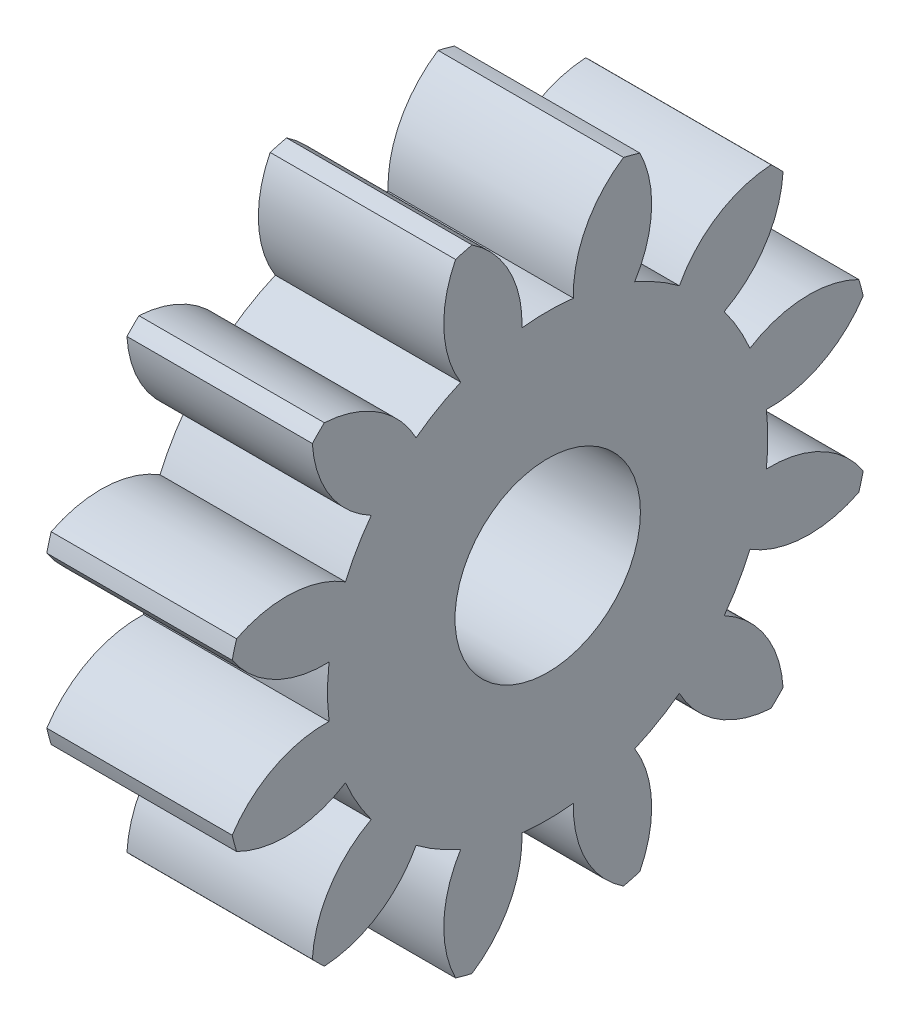
SolidWorks part; units mm, degrees
ref_plane "Plane1" through (0, 0, 0) normal (0, 0, 1) x (1, 0, 0)
ref_plane "Plane2" through (0, 0, 0) normal (0, 1, 0) x (1, 0, 0)
ref_plane "Plane3" through (0, 0, 0) normal (1, 0, 0) x (0, 0, -1)
sketch "HoldingSke" plane through (0, 0, 0) normal (0, 1, 0) x (1, 0, 0)
  line L0 (0, 0) -> (0.4891, -0.104)
  line L1 (-15, 0) -> (100, 0) construction
  line L2 (0, 0) -> (-2.1039, 2.3779)
  line L3 (0, 0) -> (-11.863, 4.5341)
  line L4 (0, 0) -> (8.4473, 1.7955)
  line L5 (0, 0) -> (-46.8476, -17.4728)
  line L6 (0, 0) -> (-6.6317, -4.4744)
  line L7 (-2.1039, 2.3779) -> (8.6586, 51.2059)
  line L8 (-76.2, 54.61) -> (-74.4, 54.61)
  line L9 (-71.009, 38.7566) -> (-53.1078, 45.2721)
  line L10 (-76.2, 71.12) -> (104.1128, 71.12)
  line L11 (0, 0) -> (-8, 0)
  line L12 (-76.2, 101.6) -> (-76.133, 101.6)
  line L13 (24.9733, 27.94) -> (52.9518, 28.4284)
  line L14 (24.9733, 27.94) -> (24.9743, 27.94)
  line L15 (24.9733, 27.94) -> (100.4006, 29.5858)
  line L16 (-63.627, -2) -> (-12.827, -2)
  circle A0 centre (0, 0) radius 5
  circle A1 centre (0, 0) radius 9.499
  circle A2 centre (0, 0) radius 37.5
  circle A3 centre (0, 0) radius 5
  dimension "Num_teeth" = 12
  dimension "Pitch_radius" = 180.3128
  dimension "Width" = 8
  dimension "Thickness" = 8
sketch "BasProSke" plane through (0, 0, 0) normal (0, 1, 0) x (1, 0, 0)
  line L0 (-10, 0) -> (60, 0) construction
  line L1 (0, 0) -> (0, 14)
  line L2 (0, 0) -> (8, 0)
  line L3 (8, 0) -> (8, 14)
  line L4 (8, 14) -> (0, 14)
  dimension "Thickness" = 8
  dimension "Diameter" = 28
revolve "Base-Revolve" add sketch "BasProSke" angle 360 about L0
sketch "TooCutSke" plane through (0, 0, 0) normal (1, 0, 0) x (0, 0, -1)
  line L1 (0, 0) -> (0, 107) construction
  line L2 (0, 0) -> (-1.6834, 11.8813) construction
  line L3 (0, 0) -> (-6.1662, 23.0126) construction
  line L4 (-1.6834, 11.8813) -> (-3.0831, 11.5063) construction
  arc A0 (1.1119, 9.4337) -> (-1.1119, 9.4337) centre (0, 0) ccw
  arc A1 (3.2981, 13.6321) -> (-3.2981, 13.6321) centre (0, 0) ccw
  circle A2 centre (0, 0) radius 12 construction
  circle A3 centre (0, 0) radius 11.2763 construction
  arc A4 (-1.1119, 9.4337) -> (-3.2981, 13.6321) centre (-5.9089, 9.6042) ccw
  arc A5 (3.2981, 13.6321) -> (1.1119, 9.4337) centre (5.9089, 9.6042) ccw
extrude "ToothCut" cut sketch "TooCutSke" along normal through all
fillet "Breaks" [suppressed] radius 0.04 tangent propagation no
fillet "RootFillets" [suppressed] radius 0.501
pattern_circular "TeethCuts" count 12 every 30 about axis through (-10, 0, 0) along (1, 0, 0) of "ToothCut", "RootFillets", "Breaks"
sketch "HubNeaOneSke" plane through (0, 0, 0) normal (-1, 0, 0) x (0, 0, 1)
  circle A0 centre (0, 0) radius 9.499
  dimension "Diameter" = 18.998
extrude "HubNearOne" [suppressed] add sketch "HubNeaOneSke" along normal blind 42.0001
sketch "HubNeaBotSke" plane through (0, 0, 0) normal (-1, 0, 0) x (0, 0, 1)
  circle A0 centre (0, 0) radius 9.499
  dimension "Diameter" = 18.998
extrude "HubNearBoth" [suppressed] add sketch "HubNeaBotSke" along normal blind 21
ref_plane "FarPln" through (8, 0, 0) normal (1, 0, 0) x (0, 0, -1)
sketch "HubFarSke" plane through (8, 0, 0) normal (1, 0, 0) x (0, 0, -1)
  circle A0 centre (0, 0) radius 9.499
  dimension "Diameter" = 18.998
extrude "HubFar" [suppressed] add sketch "HubFarSke" along normal blind 21
sketch "BorSke" plane through (0, 0, 0) normal (1, 0, 0) x (0, 0, -1)
  circle A0 centre (0, 0) radius 5
  dimension "Diameter" = 10
extrude "Bore" cut sketch "BorSke" along normal mid plane 100.0001
sketch "KeySke" plane through (0, 0, 0) normal (1, 0, 0) x (0, 0, -1)
  line L0 (-2, 0) -> (-2, 6.8)
  line L1 (-2, 6.8) -> (2, 6.8)
  line L2 (2, 6.8) -> (2, 0)
  line L3 (0, 0) -> (0, 34) construction
  line L4 (-2, 0) -> (2, 0)
  dimension "Width" = 4
extrude "Keyway" [suppressed] cut sketch "KeySke" along normal mid plane 100.0001
pattern_circular "Keyway2" [suppressed] count 2 every 90 about axis through (-10, 0, 0) along (1, 0, 0) reverse direction yes
sketch "Sketch1" plane through (8, 0, 0) normal (1, 0, 0) x (0, 0, -1)
  circle A0 centre (0, 0) radius 4
  circle A1 centre (0, 0) radius 5 construction
  circle A2 centre (0, 0) radius 5
  dimension "D1" = 8
extrude "Boss-Extrude1" add sketch "Sketch1" against normal through all
equation "' \"Module@HoldingSke\" = 6.35"
equation "' \"Num_teeth@HoldingSke\" = 12"
equation "' \"Ap@HoldingSke\" =  20"
equation "' \"Ap@HoldingSke\" = 20"
equation "' \"Width@HoldingSke\" = 0.5 * 25.4"
equation "' \"Hub_dia@HoldingSke\"= 1 * 25.4"
equation "' \"Hub_dia@HoldingSke\" = 1 * 25.4"
equation "' \"Overall_len@HoldingSke\" = 1.0 * 25.4"
equation "' \"Bore@HoldingSke\" = 0.75 * 25.4"
equation "' \"T_dim@HoldingSke\" = 0.1 * 25.4"
equation "' \"Width@KeySke\" = 0.25 * 25.4"
equation "' \"Show_teeth@HoldingSke\" = 13"
equation "' \"Backlash@HoldingSke\" = 0.009 * 25.4"
equation "' \"Addendum_fac@HoldingSke\" = 1.0"
equation "' \"Dedendum_fac@HoldingSke\" = 1.25"
equation "' \"Dedendum_add@HoldingSke\" = 0.00005 * 25.4"
equation "' \"Clearance_fac@HoldingSke\" = 0.25"
equation "\"Pitch@HoldingSke\" = 1 / \"Module@HoldingSke\""
equation "\"Overcut_dia@TooCutSke\" = (\"Num_teeth@HoldingSke\" + 2 * \"Addendum_fac@HoldingSke\") / \"Pitch@HoldingSke\" + 0.002 * 25.4"
equation "\"Pitch_dia@TooCutSke\" = \"Num_teeth@HoldingSke\" / \"Pitch@HoldingSke\""
equation "\"Base_dia@TooCutSke\" = \"Num_teeth@HoldingSke\" / \"Pitch@HoldingSke\" * cos((\"Ap@HoldingSke\"  * 3.14159265 / 180))"
equation "\"Root_dia@TooCutSke\" = (\"Num_teeth@HoldingSke\" + 2) / \"Pitch@HoldingSke\" - 2 * (\"Addendum_fac@HoldingSke\" + \"Dedendum_fac@HoldingSke\") / \"Pitch@HoldingSke\" - \"Dedendum_add@HoldingSke\" * 2"
equation "\"Half_ang@TooCutSke\" = 180 / \"Num_teeth@HoldingSke\""
equation "\"Half_CT@TooCutSke\" = \"Num_teeth@HoldingSke\" / \"Pitch@HoldingSke\" * sin((3.14159265 / 2 / \"Num_teeth@HoldingSke\")) / 2 - 7 * \"Backlash@HoldingSke\" / 4"
equation "\"Flank_rad@TooCutSke\" = \"Num_teeth@HoldingSke\" / \"Pitch@HoldingSke\" / 5"
equation "\"Radius@RootFillets\" = \"Clearance_fac@HoldingSke\" / \"Pitch@HoldingSke\" + \"Dedendum_add@HoldingSke\""
equation "\"Break_rad@Breaks\" = 0.02 / \"Pitch@HoldingSke\""
equation "\"Thickness@HoldingSke\" = \"Width@HoldingSke\""
equation "\"OAL@HoldingSke\" = \"Thickness@HoldingSke\""
equation "\"MHD@HoldingSke\" = (\"Num_teeth@HoldingSke\" + 2) / \"Pitch@HoldingSke\" - 2 * (\"Addendum_fac@HoldingSke\" + \"Dedendum_fac@HoldingSke\")  / \"Pitch@HoldingSke\" - \"Dedendum_add@HoldingSke\" * 2"
equation "\"MBD@HoldingSke\" = (\"Num_teeth@HoldingSke\" + 2) / \"Pitch@HoldingSke\" - 2 * (\"Addendum_fac@HoldingSke\" + \"Dedendum_fac@HoldingSke\")  / \"Pitch@HoldingSke\" - \"Dedendum_add@HoldingSke\" * 2 - 0.002 * 25.4"
equation "\"MHD@HoldingSke\" = ((sgn( \"MHD@HoldingSke\" - \"Hub_dia@HoldingSke\" )-1)*( \"MHD@HoldingSke\" - \"Hub_dia@HoldingSke\" ))/-2+ \"Hub_dia@HoldingSke\""
equation "\"MBD@HoldingSke\" = ((sgn( \"MBD@HoldingSke\" - \"Bore@HoldingSke\" )-1)*( \"MBD@HoldingSke\" - \"Bore@HoldingSke\" ))/-2+ \"Bore@HoldingSke\""
equation "\"OAL@HoldingSke\" = ((sgn( \"OAL@HoldingSke\" - \"Overall_len@HoldingSke\" )+1)*( \"OAL@HoldingSke\" - \"Overall_len@HoldingSke\" ))/2 + \"Overall_len@HoldingSke\" + 0.000002 * 25.4"
equation "\"Num_teeth@TeethCuts\" = int( \"Show_teeth@HoldingSke\" ) + 1"
equation "\"Num_teeth@TeethCuts\" = ((sgn( \"Num_teeth@TeethCuts\" - \"Num_teeth@HoldingSke\" )-1)*( \"Num_teeth@TeethCuts\" - \"Num_teeth@HoldingSke\" ))/-2+ \"Num_teeth@HoldingSke\""
equation "\"Num_teeth@TeethCuts\" = ((sgn( \"Num_teeth@TeethCuts\" - 2.0)+1)*( \"Num_teeth@TeethCuts\" - 2.0))/2 +2.0"
equation "\"Angle@TeethCuts\" = 360.0 / \"Num_teeth@HoldingSke\""
equation "\"Diameter@BasProSke\" = (\"Num_teeth@HoldingSke\" + 2 * \"Addendum_fac@HoldingSke\") / \"Pitch@HoldingSke\""
equation "\"Thickness@BasProSke\"  = \"Thickness@HoldingSke\""
equation "' \"Fillet_rad@BasProSke\" =  \"Thickness@HoldingSke\" * 0.05"
equation "' \"Fillet_rad@BasProSke\" = \"Thickness@HoldingSke\" * 0.05"
equation "\"MHD@HoldingSke\" = ((sgn( \"MHD@HoldingSke\" - \"Root_dia@TooCutSke\" )-1)*( \"MHD@HoldingSke\" - \"Root_dia@TooCutSke\" ))/-2+ \"Root_dia@TooCutSke\""
equation "\"Diameter@HubNeaOneSke\" = \"MHD@HoldingSke\""
equation "\"Length@HubNearOne\" = \"OAL@HoldingSke\" - \"Thickness@BasProSke\""
equation "\"Diameter@HubNeaBotSke\" = \"MHD@HoldingSke\""
equation "\"Length@HubNearBoth\" = ( \"OAL@HoldingSke\" - \"Thickness@BasProSke\" ) / 2.0"
equation "\"Thickness@FarPln\" = \"Thickness@BasProSke\""
equation "\"Diameter@HubFarSke\" = \"MHD@HoldingSke\""
equation "\"Length@HubFar\" = ( \"OAL@HoldingSke\" - \"Thickness@BasProSke\" ) / 2.0"
equation "\"Diameter@BorSke\" = \"MBD@HoldingSke\""
equation "\"D1@Bore\" = \"OAL@HoldingSke\" * 2.0"
equation "\"D1@Keyway\" = \"OAL@HoldingSke\" * 2.0"
equation "\"Offset@KeySke\" = \"T_dim@HoldingSke\" + \"MBD@HoldingSke\" / 2.0"
